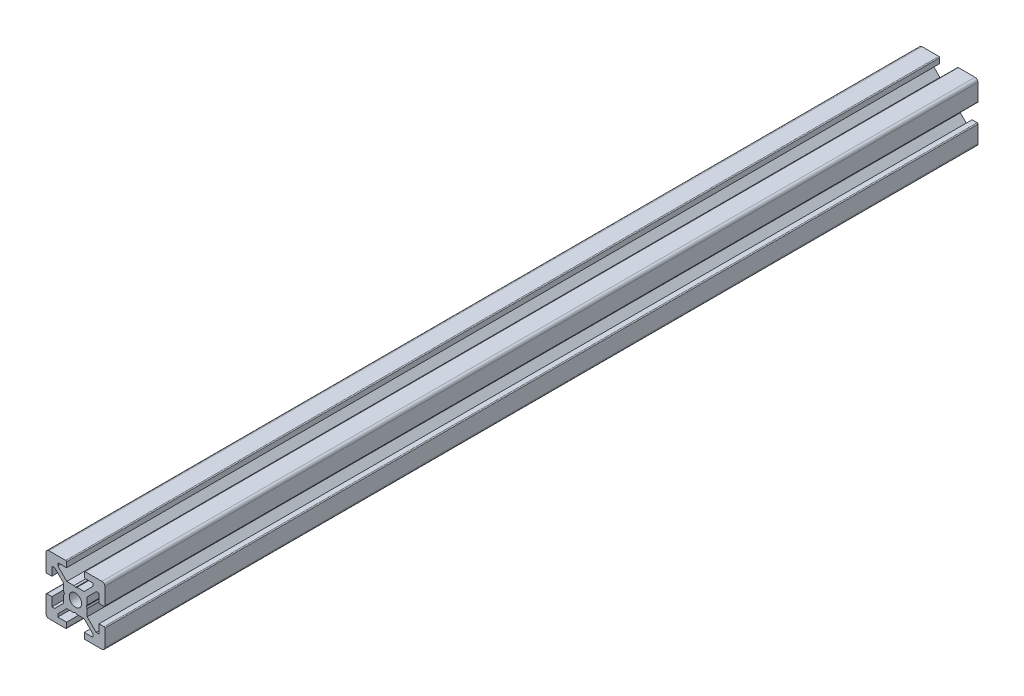
SolidWorks part; units mm, degrees
ref_plane "Front Plane" through (0, 0, 0) normal (0, 0, 1) x (1, 0, 0)
ref_plane "Top Plane" through (0, 0, 0) normal (0, 1, 0) x (1, 0, 0)
ref_plane "Right Plane" through (0, 0, 0) normal (1, 0, 0) x (0, 0, -1)
ref_plane "Plane1" through (0, 0, 0) normal (0, 0, 1) x (1, 0, 0)
sketch "Sketch1" plane through (0, 0, 0) normal (0, 0, 1) x (1, 0, 0)
  line L0 (-10, 9) -> (-10, 3.3)
  line L1 (-9.7, 3) -> (-8, 3)
  line L2 (-8, 3) -> (-8, 6)
  line L3 (-8, 6) -> (-7.0607, 6)
  line L4 (-7.0607, 6) -> (-4, 2.9393)
  line L5 (-4, 2.9393) -> (-4, 0.5196)
  line L6 (-4, 0.5196) -> (-3.7, 0)
  line L7 (-3.7, 0) -> (-4, -0.5196)
  line L8 (-4, -0.5196) -> (-4, -2.9393)
  line L9 (-4, -2.9393) -> (-7.0607, -6)
  line L10 (-7.0607, -6) -> (-8, -6)
  line L11 (-8, -6) -> (-8, -3)
  line L12 (-8, -3) -> (-9.7, -3)
  line L13 (-10, -3.3) -> (-10, -9)
  line L14 (-9, -10) -> (-3.3, -10)
  line L15 (-3, -9.7) -> (-3, -8)
  line L16 (-3, -8) -> (-6, -8)
  line L17 (-6, -8) -> (-6, -7.0607)
  line L18 (-6, -7.0607) -> (-2.9393, -4)
  line L19 (-2.9393, -4) -> (-0.5196, -4)
  line L20 (-0.5196, -4) -> (0, -3.7)
  line L21 (0, -3.7) -> (0.5196, -4)
  line L22 (0.5196, -4) -> (2.9393, -4)
  line L23 (2.9393, -4) -> (6, -7.0607)
  line L24 (6, -7.0607) -> (6, -8)
  line L25 (6, -8) -> (3, -8)
  line L26 (3, -8) -> (3, -9.7)
  line L27 (3.3, -10) -> (9, -10)
  line L28 (10, -9) -> (10, -3.3)
  line L29 (9.7, -3) -> (8, -3)
  line L30 (8, -3) -> (8, -6)
  line L31 (8, -6) -> (7.0606, -6)
  line L32 (7.0606, -6) -> (4, -2.9393)
  line L33 (4, -2.9393) -> (4, -0.5196)
  line L34 (4, -0.5196) -> (3.7, 0)
  line L35 (3.7, 0) -> (4, 0.5196)
  line L36 (4, 0.5196) -> (4, 2.9393)
  line L37 (4, 2.9393) -> (7.0607, 6)
  line L38 (7.0607, 6) -> (8, 6)
  line L39 (8, 6) -> (8, 3)
  line L40 (8, 3) -> (9.7, 3)
  line L41 (10, 3.3) -> (10, 9)
  line L42 (9, 10) -> (3.3, 10)
  line L43 (3, 9.7) -> (3, 8)
  line L44 (3, 8) -> (6, 8)
  line L45 (6, 8) -> (6, 7.0607)
  line L46 (6, 7.0607) -> (2.9393, 4)
  line L47 (2.9393, 4) -> (0.5196, 4)
  line L48 (0.5196, 4) -> (0, 3.7)
  line L49 (0, 3.7) -> (-0.5196, 4)
  line L50 (-0.5196, 4) -> (-2.9394, 4)
  line L51 (-2.9394, 4) -> (-6, 7.0606)
  line L52 (-6, 7.0606) -> (-6, 8)
  line L53 (-6, 8) -> (-3, 8)
  line L54 (-3, 8) -> (-3, 9.7)
  line L55 (-3.3, 10) -> (-9, 10)
  arc A0 (-10, 3.3) -> (-9.7, 3) centre (-9.7, 3.3) ccw
  arc A1 (-9.7, -3) -> (-10, -3.3) centre (-9.7, -3.3) ccw
  arc A2 (-10, -9) -> (-9, -10) centre (-9, -9) ccw
  arc A3 (-3.3, -10) -> (-3, -9.7) centre (-3.3, -9.7) ccw
  arc A4 (3, -9.7) -> (3.3, -10) centre (3.3, -9.7) ccw
  arc A5 (9, -10) -> (10, -9) centre (9, -9) ccw
  arc A6 (10, -3.3) -> (9.7, -3) centre (9.7, -3.3) ccw
  arc A7 (9.7, 3) -> (10, 3.3) centre (9.7, 3.3) ccw
  arc A8 (10, 9) -> (9, 10) centre (9, 9) ccw
  arc A9 (3.3, 10) -> (3, 9.7) centre (3.3, 9.7) ccw
  arc A10 (-3, 9.7) -> (-3.3, 10) centre (-3.3, 9.7) ccw
  arc A11 (-9, 10) -> (-10, 9) centre (-9, 9) ccw
extrude "Boss-Extrude1" add sketch "Sketch1" against normal blind 296.6
ref_plane "Plane2" through (0, 0, 0) normal (1, 0, 0) x (0, 0, -1)
sketch "Sketch2" plane through (0, 0, 0) normal (1, 0, 0) x (0, 0, -1)
  line L0 (0, 0) -> (0, 2.1)
  line L1 (0, 2.1) -> (355, 2.1)
  line L2 (355, 2.1) -> (355, 0)
  line L3 (355, 0) -> (0, 0)
  line L4 (355, 0) -> (0, 0) construction
revolve "Cut-Revolve1" cut sketch "Sketch2" angle 360 about L4 reverse direction yes
ref_plane "Plane3" through (0, 0, 0) normal (1, 0, 0) x (0, 0, -1)
sketch "Sketch3" plane through (0, 0, 0) normal (1, 0, 0) x (0, 0, -1)
  circle A0 centre (177.5, 0) radius 3.6751
extrude "Cut-Extrude1" [suppressed] cut sketch "Sketch3" against normal blind 10 and the other way blind 10
ref_plane "Plane4" through (0, 0, -148.3) normal (0, 0, 1) x (1, 0, 0)
